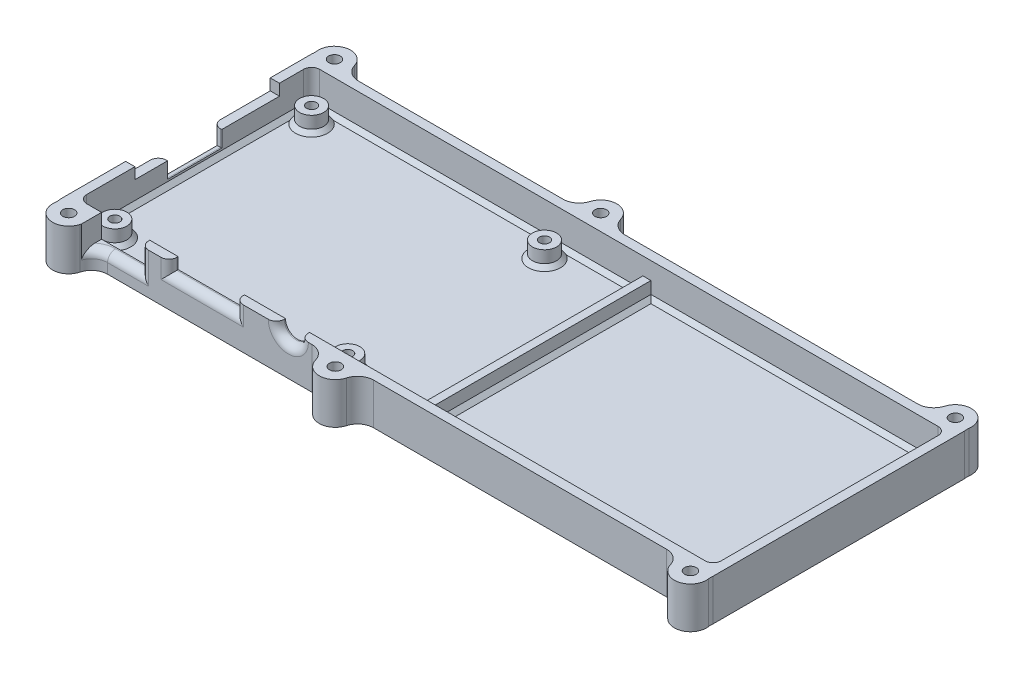
SolidWorks part; units mm, degrees
ref_plane "Front Plane" through (0, 0, 0) normal (0, 0, 1) x (1, 0, 0)
ref_plane "Top Plane" through (0, 0, 0) normal (0, 1, 0) x (1, 0, 0)
ref_plane "Right Plane" through (0, 0, 0) normal (1, 0, 0) x (0, 0, -1)
sketch "Sketch1" plane through (0, 0, 0) normal (0, 1, 0) x (1, 0, 0)
  line L0 (-71.5618, 3.106) -> (84.4382, 3.106) construction
  line L1 (-71.5618, 31.106) -> (84.4382, 31.106)
  line L2 (-71.5618, 31.106) -> (-71.5618, -24.894)
  line L3 (-71.5618, -24.894) -> (84.4382, -24.894)
  line L4 (84.4382, 31.106) -> (84.4382, -24.894)
  line L5 (-60.6618, -24.894) -> (-60.6618, -31.6828) construction
  line L6 (-68.0618, 27.606) -> (-10.0618, 27.606)
  line L7 (-68.0618, 27.606) -> (-68.0618, -21.394)
  line L8 (-68.0618, -21.394) -> (-10.0618, -21.394)
  line L9 (-10.0618, 27.606) -> (-10.0618, -21.394)
  line L10 (-39.5618, -24.894) -> (-39.5618, -31.6828) construction
  line L11 (-18.0618, -24.894) -> (-18.0618, -31.6828) construction
  line L12 (-65.4118, -26.5648) -> (-55.9118, -26.5648) construction
  line L13 (-48.0618, -26.5648) -> (-31.0618, -26.5648) construction
  line L14 (-22.0618, -26.5648) -> (-14.0618, -26.5648) construction
  line L15 (-72.5618, 9.606) -> (-72.5618, -3.394) construction
  line L16 (-71.5618, 3.106) -> (-72.5618, 3.106) construction
  dimension "D1" = 156
  dimension "D2" = 56
  dimension "D3" = 49
  dimension "D4" = 58
  dimension "D5" = 3.5
  dimension "D6" = 3.5
  dimension "D7" = 10.9
  dimension "D8" = 32
  dimension "D9" = 53.5
  dimension "D10" = 2
  dimension "D11" = 13
  dimension "D12" = 9.5
  dimension "D13" = 17
  dimension "D14" = 8
sketch "Sketch3" plane through (0, 0, 0) normal (0, 1, 0) x (1, 0, 0)
  line L4 (87.7382, 34.406) -> (-74.8618, 34.406)
  line L5 (-74.8618, 34.406) -> (-74.8618, -28.194)
  line L6 (-74.8618, -28.194) -> (87.7382, -28.194)
  line L7 (87.7382, -28.194) -> (87.7382, 34.406)
  line L8 (85.4382, 32.106) -> (-72.5618, 32.106)
  line L9 (85.4382, -25.894) -> (85.4382, 32.106)
  line L10 (-72.5618, -25.894) -> (85.4382, -25.894)
  line L11 (-72.5618, 32.106) -> (-72.5618, -25.894)
  line L12 (85.4382, 32.106) -> (-72.5618, 32.106)
  line L13 (85.4382, -25.894) -> (85.4382, 32.106)
  line L14 (-72.5618, -25.894) -> (85.4382, -25.894)
  line L15 (-72.5618, 32.106) -> (-72.5618, -25.894)
  line L16 (6.4382, 3.106) -> (6.4382, 34.406) construction
  line L17 (-71.5618, 3.106) -> (84.4382, 3.106) construction
  line L20 (-74.8618, 3.106) -> (87.7382, 3.106) construction
  dimension "D1" = 1
  dimension "D2" = 2.3
extrude "Boss-Extrude1" add sketch "Sketch3" along normal blind 10.3
sketch "Sketch5" plane through (0, 0, 0) normal (0, 1, 0) x (1, 0, 0)
  line L1 (-72.5618, 32.106) -> (85.4382, 32.106)
  line L2 (-72.5618, 32.106) -> (-72.5618, -25.894)
  line L3 (-72.5618, -25.894) -> (85.4382, -25.894)
  line L4 (85.4382, 32.106) -> (85.4382, -25.894)
extrude "Boss-Extrude2" add sketch "Sketch5" along normal blind 2
sketch "Sketch6" plane through (0, 2, 0) normal (0, 1, 0) x (1, 0, 0)
  circle A0 centre (-68.0618, 27.606) radius 3
  circle A1 centre (-68.0618, -21.394) radius 3
  circle A2 centre (-10.0618, -21.394) radius 3
  circle A3 centre (-10.0618, 27.606) radius 3
extrude "Boss-Extrude3" add sketch "Sketch6" along normal blind 4
hole_wizard "Ø2.5 (2.5) Diameter Hole1" positions "Sketch8" profile "Sketch9" hole size "Ø2.5" standard "ANSI Metric"
sketch "Sketch8" plane through (0, 6, 0) normal (0, 1, 0) x (1, 0, 0)
  point P0 (-68.0618, 27.606)
  point P3 (-10.0618, 27.606)
  point P6 (-10.0618, -21.394)
  point P9 (-68.0618, -21.394)
sketch "Sketch9" plane through (-68.0618, 6, -27.606) normal (1, 0, 0) x (0, 0, 1)
  line L0 (0, 0) -> (0, 8.7511)
  line L1 (0, 8.7511) -> (1.25, 8)
  line L2 (1.25, 8) -> (1.25, 0)
  line L5 (1.25, 0) -> (0, 0)
  line L10 (0, 8.7511) -> (-1.25, 8) construction
  line L11 (0, -6.35) -> (0, 107.95) construction
  dimension "Hole Dia." = 2.5
  dimension "Hole Depth" = 8
  dimension "Drill Angle" = 118
sketch "Sketch10" plane through (0, 2, 0) normal (0, 1, 0) x (1, 0, 0)
  line L0 (85.4382, 32.106) -> (-72.5618, 32.106) construction
  line L1 (9.9382, 32.106) -> (11.9382, 32.106)
  line L2 (9.9382, 32.106) -> (9.9382, -25.894)
  line L3 (9.9382, -25.894) -> (11.9382, -25.894)
  line L4 (11.9382, 32.106) -> (11.9382, -25.894)
  line L5 (-72.5618, -25.894) -> (85.4382, -25.894) construction
  line L6 (-10.0618, 27.606) -> (-10.0618, -21.394) construction
  dimension "D1" = 2
  dimension "D2" = 20
extrude "Boss-Extrude4" add sketch "Sketch10" along normal blind 4
sketch "Sketch11" plane through (0, 0, 28.194) normal (0, 0, 1) x (1, 0, 0)
  line L0 (-74.8618, 10.3) -> (-74.8618, 0) construction
  line L1 (-66.8618, 10.3) -> (-54.8618, 10.3)
  line L2 (-66.8618, 10.3) -> (-66.8618, 4.5)
  line L3 (-66.8618, 4.5) -> (-54.8618, 4.5)
  line L4 (-54.8618, 10.3) -> (-54.8618, 4.5)
  line L5 (-74.8618, 0) -> (87.7382, 0) construction
  line L6 (-60.8618, 10.3) -> (-60.6618, 0) construction
  line L7 (-65.4118, 0) -> (-55.9118, 0) construction
  line L9 (-47.778, 10.3) -> (-31.278, 10.3)
  line L10 (-47.778, 10.3) -> (-47.778, 7.5)
  line L11 (-47.778, 7.5) -> (-31.278, 7.5)
  line L12 (-31.278, 10.3) -> (-31.278, 7.5)
  line L13 (-68.0618, 0) -> (-10.0618, 0) construction
  line L14 (-39.5618, 0) -> (-39.528, 10.3) construction
  line L15 (-48.0618, 0) -> (-31.0618, 0) construction
  line L16 (-18.0618, 0) -> (-18.0618, 10.3) construction
  line L17 (-22.0618, 0) -> (-14.0618, 0) construction
  line L18 (-74.8618, 10.3) -> (87.7382, 10.3) construction
  circle A0 centre (-18.0618, 10.3) radius 3
  dimension "D5" = 6
  dimension "D1" = 4.5
  dimension "D2" = 12
  dimension "D3" = 7.5
  dimension "D4" = 16.5
  dimension "D6" = 8
extrude "Cut-Extrude1" cut sketch "Sketch11" against normal up to next
sketch "Sketch12" plane through (-74.8618, 0, 0) normal (-1, 0, 0) x (0, 0, 1)
  line L0 (-3.106, 0) -> (-3.106, 10.3) construction
  line L1 (-27.606, 0) -> (21.394, 0) construction
  line L2 (-34.406, 10.3) -> (28.194, 10.3) construction
  line L4 (-9.7329, 10.3) -> (3.7671, 10.3)
  line L5 (-9.7329, 10.3) -> (-9.7329, 3.5)
  line L6 (-9.7329, 3.5) -> (3.7671, 3.5)
  line L7 (3.7671, 10.3) -> (3.7671, 3.5)
  line L8 (-24.106, 10.3) -> (11.894, 10.3)
  line L9 (-24.106, 10.3) -> (-24.106, 7.5)
  line L10 (-24.106, 7.5) -> (11.894, 7.5)
  line L11 (11.894, 10.3) -> (11.894, 7.5)
  dimension "D1" = 13.5
  dimension "D2" = 3.5
  dimension "D3" = 7.5
  dimension "D4" = 36
extrude "Cut-Extrude2" cut sketch "Sketch12" against normal up to next contours L10 L11 L8 L9 | L7 L6 L5 L4
sketch "Sketch13" plane through (0, 0, 0) normal (0, 1, 0) x (1, 0, 0)
  line L0 (-74.8618, 34.406) -> (-74.8618, 42.3177) construction
  line L1 (87.7382, 34.406) -> (87.7382, 40.5826) construction
  line L2 (-74.8618, 2.9829) -> (87.7382, 3.106) construction
  line L3 (-74.8618, 9.7329) -> (-74.8618, -3.7671) construction
  line L4 (9.9382, 32.106) -> (-72.5618, 32.106) construction
  line L5 (87.7382, -28.194) -> (87.7382, 34.406) construction
  circle A0 centre (-70.8618, 36.106) radius 4
  circle A1 centre (-4.5618, 36.106) radius 4
  circle A2 centre (83.7382, 36.106) radius 4
  circle A3 centre (83.7882, -29.9) radius 4
  circle A4 centre (-4.5117, -30.0337) radius 4
  circle A5 centre (-70.8116, -30.1341) radius 4
  dimension "D1" = 4
  dimension "D3" = 4
  dimension "D2" = 4
extrude "Boss-Extrude5" add sketch "Sketch13" along normal up to vertex (10.3 mm away) up to point (-15.0618, 10.3, 28.194)
fillet "Fillet2" radius 4 1 edges at (-74.4825, 5.15, -34.406)
fillet "Fillet3" radius 4 8 edges at (80.1703, 5.15, 28.194) (-67.3136, 5.15, 28.194) (-0.9599, 5.15, 28.194) (-8.0635, 5.15, 28.194) (80.1175, 5.15, -34.406) (-0.941, 5.15, -34.406) (-8.1825, 5.15, -34.406) (-67.241, 5.15, -34.406)
fillet "Fillet4" radius 4 3 edges at (-74.3097, 5.15, 28.194) (87.4061, 5.15, 28.194) (87.359, 5.15, -34.406)
hole_wizard "Ø2.9 (2.9) Diameter Hole1" positions "Sketch15" profile "Sketch16" hole size "Ø2.9" standard "ANSI Metric" end condition up to next
sketch "Sketch15" plane through (0, 10.3, 0) normal (0, 1, 0) x (1, 0, 0)
  point P0 (-70.8618, 36.106)
  point P3 (-4.5618, 36.106)
  point P6 (83.7382, 36.106)
  point P9 (83.7882, -29.9)
  point P12 (-4.5117, -30.0337)
  point P15 (-70.8116, -30.1341)
sketch "Sketch16" plane through (-70.8618, 10.3, -36.106) normal (1, 0, 0) x (0, 0, 1)
  line L0 (0, 0) -> (0, 10.3)
  line L1 (0, 10.3) -> (1.45, 10.3)
  line L2 (1.45, 10.3) -> (1.45, 0)
  line L5 (1.45, 0) -> (0, 0)
  line L11 (0, -6.35) -> (0, 107.95) construction
  dimension "Thru Hole Dia." = 2.9
  dimension "Thru Hole Depth" = 10.3
fillet "Fillet6" radius 2 1 edges at (85.4382, 6.15, -32.106)
fillet "Fillet7" radius 2 1 edges at (85.4382, 6.15, 25.894)
fillet "Fillet8" radius 2 2 edges at (-72.5618, 6.15, 25.894) (-72.5618, 6.15, -32.106)
chamfer "Chamfer1" distance 1 angle 45 4 edges at (-68.0618, 2, 24.394) (-10.0618, 2, 24.394) (-10.0618, 2, -24.606) (-68.0618, 2, -24.606)
chamfer "Chamfer2" distance 1 angle 45 12 edges at (11.9382, 2, -3.106) (47.6882, 2, 25.894) (47.6882, 2, -32.106) (84.8524, 2, 25.3082) (84.8524, 2, -31.5202) (85.4382, 2, -3.106) (-30.3118, 2, 25.894) (-71.976, 2, 25.3082) (-72.5618, 2, -3.106) (-71.976, 2, -31.5202) (9.9382, 2, -3.106) (-30.3118, 2, -32.106)
sketch "Sketch17" plane through (0, 0, 28.194) normal (0, 0, 1) x (1, 0, 0)
  line L0 (-53.9318, 4.5) -> (-63.0738, 4.5) construction
  line L1 (-66.9465, 10.3) -> (-54.9465, 10.3)
  line L2 (-66.9465, 10.3) -> (-66.9465, 4.5)
  line L3 (-66.9465, 4.5) -> (-54.9465, 4.5)
  line L4 (-54.9465, 10.3) -> (-54.9465, 4.5)
  dimension "D1" = 12
fillet "Fillet9" radius 2 10 edges at (-65.4021, 4.5, 28.936) (-74.8618, 5.5, -9.7329) (-74.8618, 3.5, -2.9829) (-74.8618, 5.5, 3.7671) (-18.0618, 7.3, 28.194) (-31.278, 8.9, 28.194) (-47.778, 8.9, 28.194) (-39.528, 7.5, 28.194) (-54.8618, 7.4, 28.194) (-58.9716, 4.5, 28.194)
